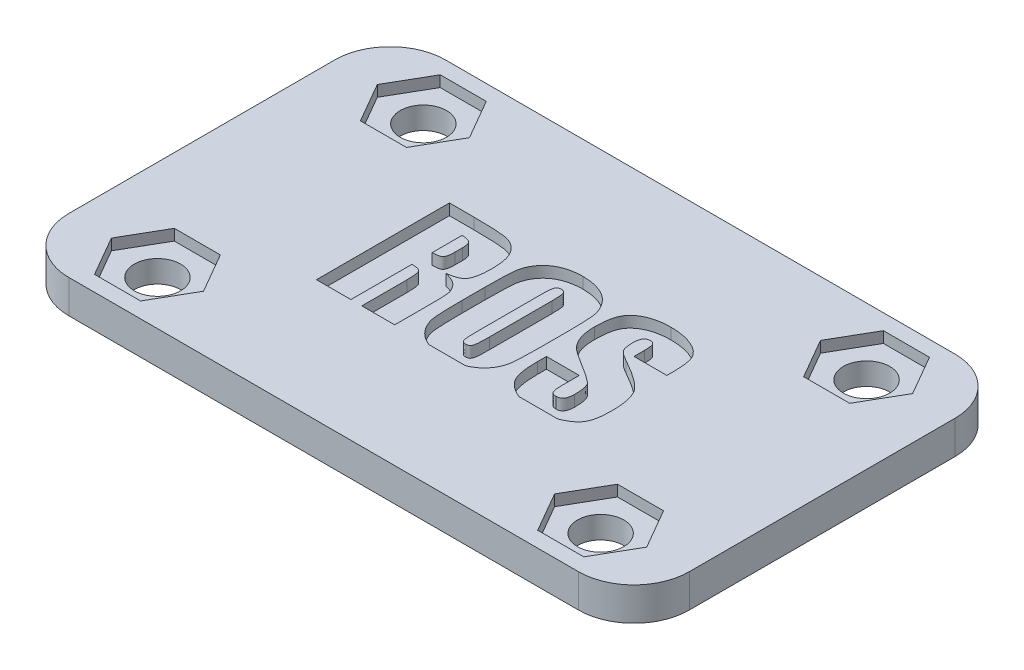
SolidWorks part; units mm, degrees
ref_plane "Front Plane" through (0, 0, 0) normal (0, 0, 1) x (1, 0, 0)
ref_plane "Top Plane" through (0, 0, 0) normal (0, 1, 0) x (1, 0, 0)
ref_plane "Right Plane" through (0, 0, 0) normal (1, 0, 0) x (0, 0, -1)
sketch "Sketch1" plane through (0, 0, 0) normal (0, 1, 0) x (1, 0, 0)
  line L1 (-28, 17) -> (28, 17)
  line L2 (-28, 17) -> (-28, -17)
  line L3 (-28, -17) -> (28, -17)
  line L4 (28, 17) -> (28, -17)
  line L5 (-28, 17) -> (28, -17) construction
  line L6 (-28, -17) -> (28, 17) construction
  point P0 (0, 0)
  dimension "D1" = 34
  dimension "D2" = 56
extrude "Boss-Extrude1" add sketch "Sketch1" along normal blind 3
sketch "Sketch2" plane through (0, 3, 0) normal (0, 1, 0) x (1, 0, 0)
  circle A0 centre (-20, 12) radius 2.09
  circle A1 centre (-20, -12) radius 2.09
  dimension "D1" = 4.18
  dimension "D2" = 24
  dimension "D3" = 12
  dimension "D4" = 20
extrude "Cut-Extrude1" cut sketch "Sketch2" against normal through all
mirror "Mirror1" about plane through (0, 0, 0) normal (1, 0, 0) of "Cut-Extrude1"
fillet "Fillet1" radius 5 4 edges at (28, 1.5, -17) (28, 1.5, 17) (-28, 1.5, 17) (-28, 1.5, -17)
sketch "Sketch3" plane through (0, 3, 0) normal (0, 1, 0) x (1, 0, 0)
  line L1 (-15.8431, 12) -> (-17.9215, 15.6)
  line L2 (-17.9215, 15.6) -> (-22.0785, 15.6)
  line L3 (-22.0785, 15.6) -> (-24.1569, 12)
  line L4 (-24.1569, 12) -> (-22.0785, 8.4)
  line L5 (-22.0785, 8.4) -> (-17.9215, 8.4)
  line L6 (-17.9215, 8.4) -> (-15.8431, 12)
  line L7 (24.1569, 12) -> (22.0785, 15.6)
  line L8 (22.0785, 15.6) -> (17.9215, 15.6)
  line L9 (17.9215, 15.6) -> (15.8431, 12)
  line L10 (15.8431, 12) -> (17.9215, 8.4)
  line L11 (17.9215, 8.4) -> (22.0785, 8.4)
  line L12 (22.0785, 8.4) -> (24.1569, 12)
  line L13 (-23, -17) -> (23, -17) construction
  circle A0 centre (-20, 12) radius 3.6 construction
  circle A1 centre (20, 12) radius 3.6 construction
  circle A2 centre (-20, 12) radius 2.09 construction
  circle A3 centre (20, 12) radius 2.09 construction
  dimension "D1" = 7.2
extrude "Cut-Extrude2" cut sketch "Sketch3" against normal blind 1
mirror "Mirror2" about plane through (0, 0, 0) normal (0, 0, 1) of "Cut-Extrude2"
sketch "Sketch4" plane through (0, 3, 0) normal (0, 1, 0) x (1, 0, 0)
  line L0 (-17, -6) -> (17, -6)
  line L1 (-11.6471, 6) -> (-9.4103, 6)
  line L2 (-4.5882, -2.7949) -> (-4.5882, -6)
  line L3 (-4.5882, -6) -> (-7.5529, -6)
  line L4 (-7.5529, -6) -> (-7.5529, -1.9412)
  line L5 (-8.5412, -0.4941) -> (-8.5412, -6)
  line L6 (-8.5412, -6) -> (-11.6471, -6)
  line L7 (-11.6471, -6) -> (-11.6471, 6)
  line L8 (-8.5412, 4.0235) -> (-8.5412, 1.3412)
  line L9 (-7.5529, 2.4287) -> (-7.5529, 3.0926)
  line L10 (-3.4588, -1.0324) -> (-3.4588, 1.0324)
  line L11 (3.7412, 1.0324) -> (3.7412, -1.0324)
  line L12 (-0.3529, 2.9757) -> (-0.3529, -2.7397)
  line L13 (0.6353, -2.6493) -> (0.6353, 2.9757)
  line L14 (11.6471, 2.3294) -> (8.6824, 2.3294)
  line L15 (8.6824, 2.3294) -> (8.6824, 3.2779)
  line L16 (4.7294, -2.4287) -> (4.7294, -1.6235)
  line L17 (4.7294, -1.6235) -> (7.6941, -1.6235)
  line L18 (7.6941, -1.6235) -> (7.6941, -3.1787)
  line L19 (11.6471, 2.8125) -> (11.6471, 2.3294)
  spline S0 degree 3 poles (-9.4103, 6) (-9.0669, 6.0012) (-8.5749, 5.9955) (-7.9492, 5.9771) (-7.5475, 5.9606) (-7.1909, 5.9363) (-6.8797, 5.9081) (-6.6138, 5.8763) (-6.3865, 5.8368) (-6.1862, 5.7853) (-6.0014, 5.7178) (-5.8245, 5.6374) (-5.6576, 5.5369) (-5.502, 5.419) (-5.352, 5.2894) (-5.2155, 5.1388) (-5.0841, 4.9743) (-4.9654, 4.7866) (-4.865, 4.5736) (-4.7788, 4.3358) (-4.7089, 4.0722) (-4.6548, 3.7831) (-4.5993, 3.3474) (-4.5915, 3.0059) (-4.5882, 2.7706) knots 0 0 0 0 0.148881 0.213303 0.271377 0.323138 0.368276 0.406827 0.439217 0.468212 0.496346 0.524443 0.552325 0.580569 0.609028 0.638128 0.668547 0.700209 0.734143 0.770448 0.80973 0.852244 0.897872 1 1 1 1
  spline S1 degree 3 poles (-4.5882, 2.7706) (-4.5847, 2.5592) (-4.5991, 2.256) (-4.6321, 1.8709) (-4.6732, 1.6245) (-4.7199, 1.4058) (-4.7787, 1.2138) (-4.8506, 1.0509) (-4.9341, 0.9125) (-5.0352, 0.7962) (-5.1554, 0.6939) (-5.2985, 0.6065) (-5.4611, 0.5289) (-5.6443, 0.4631) (-5.9295, 0.3905) (-6.1567, 0.3569) (-6.3154, 0.3441) knots 0 0 0 0 0.18379 0.264137 0.336087 0.400976 0.458649 0.510492 0.555595 0.598692 0.64408 0.692369 0.744168 0.800637 0.861472 1 1 1 1
  spline S2 degree 3 poles (-6.3154, 0.3441) (-6.1721, 0.3049) (-5.9643, 0.2494) (-5.706, 0.1522) (-5.5411, 0.0744) (-5.3931, -0.0045) (-5.2653, -0.0902) (-5.1556, -0.181) (-5.0387, -0.3053) (-4.9212, -0.4619) (-4.8041, -0.6448) (-4.7194, -0.8218) (-4.6697, -0.9719) (-4.6478, -1.1078) (-4.6293, -1.2429) (-4.6181, -1.4146) (-4.6068, -1.622) (-4.5986, -1.8647) (-4.5883, -2.2595) (-4.5915, -2.5736) (-4.5882, -2.7949) knots 0 0 0 0 0.11023 0.159227 0.204341 0.24532 0.283418 0.318243 0.350629 0.40972 0.463107 0.511383 0.554826 0.57974 0.613275 0.655917 0.707227 0.767226 0.835926 1 1 1 1
  spline S3 degree 3 poles (-7.5529, -1.9412) (-7.5542, -1.7934) (-7.554, -1.5834) (-7.5737, -1.3189) (-7.5901, -1.1553) (-7.6124, -1.0148) (-7.6369, -0.8974) (-7.67, -0.8034) (-7.7079, -0.7287) (-7.7573, -0.6684) (-7.8245, -0.6234) (-7.9036, -0.5807) (-8.0005, -0.548) (-8.1132, -0.5251) (-8.2947, -0.5004) (-8.4396, -0.4949) (-8.5412, -0.4941) knots 0 0 0 0 0.208712 0.296135 0.374434 0.440653 0.497065 0.543362 0.580978 0.614872 0.652041 0.694298 0.741574 0.795735 0.856514 1 1 1 1
  spline S4 degree 3 poles (-8.5412, 1.3412) (-8.3851, 1.3403) (-8.1682, 1.3525) (-7.9124, 1.4151) (-7.791, 1.4674) (-7.718, 1.5343) (-7.6711, 1.6021) (-7.6355, 1.6922) (-7.6049, 1.8009) (-7.5815, 1.9295) (-7.5561, 2.1403) (-7.5563, 2.3097) (-7.5529, 2.4287) knots 0 0 0 0 0.26319 0.361521 0.442778 0.481273 0.526535 0.580255 0.643242 0.716208 0.799609 1 1 1 1
  spline S5 degree 3 poles (-7.5529, 3.0926) (-7.5545, 3.251) (-7.5655, 3.4729) (-7.66, 3.7254) (-7.7586, 3.8532) (-7.9007, 3.9314) (-8.1584, 4.0148) (-8.3828, 4.0205) (-8.5412, 4.0235) knots 0 0 0 0 0.296724 0.405999 0.497474 0.590179 0.702697 1 1 1 1
  spline S6 degree 3 poles (3.7412, -1.0324) (3.7385, -1.3125) (3.74, -1.7169) (3.7317, -2.2339) (3.7191, -2.5721) (3.71, -2.8766) (3.6939, -3.1487) (3.6767, -3.3877) (3.6517, -3.661) (3.6003, -3.9749) (3.4883, -4.3317) (3.3296, -4.6711) (3.1303, -4.9928) (2.887, -5.2876) (2.6016, -5.5477) (2.2768, -5.7719) (1.913, -5.9572) (1.5147, -6.1011) (0.926, -6.2488) (0.4589, -6.2785) (0.1412, -6.2824) knots 0 0 0 0 0.112809 0.162854 0.208179 0.249065 0.285542 0.317902 0.345566 0.396043 0.445676 0.495616 0.546553 0.597656 0.649001 0.701564 0.75612 0.812885 0.871769 1 1 1 1
  spline S7 degree 3 poles (0.1412, -6.2824) (-0.1648, -6.2831) (-0.6144, -6.2452) (-1.1897, -6.1149) (-1.5848, -5.9757) (-1.9508, -5.7992) (-2.2779, -5.5765) (-2.5736, -5.321) (-2.8223, -5.0216) (-3.0318, -4.6996) (-3.1943, -4.3589) (-3.3103, -4.0053) (-3.368, -3.6952) (-3.392, -3.4245) (-3.4096, -3.1854) (-3.4246, -2.9111) (-3.4383, -2.603) (-3.4461, -2.2596) (-3.4555, -1.7324) (-3.458, -1.3191) (-3.4588, -1.0324) knots 0 0 0 0 0.123179 0.180929 0.237119 0.291548 0.344027 0.396062 0.448383 0.50021 0.550408 0.599943 0.649656 0.677029 0.709392 0.746168 0.787661 0.833574 0.884513 1 1 1 1
  spline S8 degree 3 poles (-3.4588, 1.0324) (-3.4561, 1.3132) (-3.4578, 1.7177) (-3.4492, 2.2346) (-3.437, 2.5721) (-3.4266, 2.8773) (-3.4146, 3.1495) (-3.3962, 3.3884) (-3.3721, 3.6612) (-3.3171, 3.9747) (-3.206, 4.3317) (-3.0479, 4.6709) (-2.8464, 4.9909) (-2.6056, 5.2885) (-2.3171, 5.546) (-1.9944, 5.773) (-1.63, 5.9562) (-1.2327, 6.1053) (-0.6417, 6.2443) (-0.1769, 6.2856) (0.1412, 6.2824) knots 0 0 0 0 0.1131 0.162847 0.20817 0.249054 0.28581 0.317873 0.345536 0.396062 0.445693 0.495631 0.546315 0.597643 0.649205 0.701523 0.756077 0.812942 0.872041 1 1 1 1
  spline S9 degree 3 poles (0.1412, 6.2824) (0.4469, 6.2818) (0.8967, 6.2477) (1.4702, 6.1117) (1.8645, 5.9733) (2.2316, 5.7988) (2.5599, 5.5778) (2.8536, 5.3201) (3.1028, 5.0218) (3.3114, 4.6989) (3.4772, 4.3595) (3.5927, 4.0046) (3.6506, 3.6938) (3.6735, 3.4229) (3.6959, 3.1849) (3.7057, 2.911) (3.7213, 2.6031) (3.7275, 2.2595) (3.7434, 1.7325) (3.7366, 1.3191) (3.7412, 1.0324) knots 0 0 0 0 0.123202 0.180743 0.236944 0.291253 0.343988 0.395811 0.448142 0.499979 0.550314 0.59986 0.649873 0.677251 0.709348 0.746116 0.787617 0.833538 0.884493 1 1 1 1
  spline S10 degree 3 poles (0.6353, 2.9757) (0.6349, 3.1052) (0.6314, 3.2898) (0.6236, 3.523) (0.6121, 3.6693) (0.5991, 3.7965) (0.585, 3.9051) (0.5651, 3.9935) (0.5377, 4.0836) (0.4873, 4.1724) (0.3682, 4.2858) (0.2378, 4.3035) (0.1566, 4.3059) knots 0 0 0 0 0.245382 0.350014 0.44228 0.523563 0.592561 0.649714 0.69512 0.770679 0.840726 1 1 1 1
  spline S11 degree 3 poles (0.1566, 4.3059) (0.0809, 4.3097) (-0.0301, 4.2831) (-0.155, 4.2004) (-0.2173, 4.1263) (-0.2587, 4.0467) (-0.283, 3.962) (-0.3051, 3.8552) (-0.3211, 3.7245) (-0.3378, 3.5709) (-0.3473, 3.3184) (-0.3544, 3.1178) (-0.3529, 2.9757) knots 0 0 0 0 0.141273 0.207934 0.278501 0.320511 0.375555 0.443281 0.525523 0.622695 0.733336 1 1 1 1
  spline S12 degree 3 poles (-0.3529, -2.7397) (-0.3502, -2.9007) (-0.3519, -3.1295) (-0.3437, -3.4171) (-0.331, -3.5941) (-0.3222, -3.7459) (-0.3063, -3.8724) (-0.2896, -3.9735) (-0.2657, -4.0719) (-0.2162, -4.1673) (-0.0898, -4.2859) (0.0478, -4.3054) (0.1346, -4.3059) knots 0 0 0 0 0.263966 0.37491 0.47152 0.554902 0.624119 0.680394 0.722784 0.789642 0.853612 1 1 1 1
  spline S13 degree 3 poles (0.1346, -4.3059) (0.2255, -4.3075) (0.3671, -4.2777) (0.4949, -4.1446) (0.5422, -4.0365) (0.5704, -3.9275) (0.586, -3.8179) (0.6017, -3.6841) (0.615, -3.5252) (0.6226, -3.3412) (0.6323, -3.0464) (0.6344, -2.8132) (0.6353, -2.6493) knots 0 0 0 0 0.145036 0.209347 0.281953 0.327187 0.385478 0.455017 0.538188 0.634996 0.743262 1 1 1 1
  spline S14 degree 3 poles (8.6824, 3.2779) (8.6818, 3.4588) (8.6776, 3.7029) (8.6263, 3.9859) (8.5738, 4.1183) (8.4978, 4.207) (8.3666, 4.2877) (8.2475, 4.3082) (8.1662, 4.3059) knots 0 0 0 0 0.412843 0.553103 0.65361 0.73318 0.814494 1 1 1 1
  spline S15 degree 3 poles (8.1662, 4.3059) (8.076, 4.3052) (7.9379, 4.2803) (7.7902, 4.1738) (7.6998, 4.0667) (7.6311, 3.9284) (7.5692, 3.6856) (7.549, 3.4865) (7.5529, 3.3441) knots 0 0 0 0 0.212113 0.312859 0.418563 0.535756 0.66915 1 1 1 1
  spline S16 degree 3 poles (7.5529, 3.3441) (7.5516, 3.1611) (7.5694, 2.8413) (7.6434, 2.5283) (7.7029, 2.4044) knots 0 0 0 0 0.572651 1 1 1 1
  spline S17 degree 3 poles (7.7029, 2.4044) (7.7322, 2.3452) (7.7942, 2.2581) (7.8995, 2.147) (8.0059, 2.059) (8.1288, 1.9644) (8.3296, 1.8295) (8.496, 1.7357) (8.6118, 1.6699) knots 0 0 0 0 0.166753 0.269572 0.387216 0.516182 0.662459 1 1 1 1
  spline S18 degree 3 poles (8.6118, 1.6699) (8.9472, 1.484) (9.4257, 1.211) (10.0156, 0.8328) (10.3851, 0.5738) (10.7061, 0.3313) (11.0411, 0.0406) (11.2578, -0.1815) (11.3669, -0.3397) knots 0 0 0 0 0.335278 0.4813 0.612364 0.729739 0.832713 1 1 1 1
  spline S19 degree 3 poles (11.3669, -0.3397) (11.4674, -0.4836) (11.5941, -0.7269) (11.7151, -1.0863) (11.7938, -1.3946) (11.8552, -1.7344) (11.9148, -2.2468) (11.9294, -2.6482) (11.9294, -2.925) knots 0 0 0 0 0.195997 0.304678 0.423526 0.551406 0.690506 1 1 1 1
  spline S20 degree 3 poles (11.9294, -2.925) (11.9306, -3.1274) (11.921, -3.4206) (11.8877, -3.7962) (11.8559, -4.046) (11.8113, -4.2742) (11.7592, -4.4814) (11.6979, -4.6686) (11.6247, -4.8366) (11.5365, -4.9904) (11.4313, -5.1345) (11.31, -5.2737) (11.1701, -5.4062) (11.0125, -5.5328) (10.8359, -5.6506) (10.6422, -5.7639) (10.3591, -5.9089) (9.9729, -6.059) (9.2933, -6.2392) (8.7537, -6.28) (8.3868, -6.2824) knots 0 0 0 0 0.107307 0.155459 0.199907 0.240819 0.278648 0.313174 0.345124 0.37569 0.406967 0.439576 0.4735 0.509002 0.546638 0.58596 0.627987 0.715167 0.805112 1 1 1 1
  spline S21 degree 3 poles (8.3868, -6.2824) (8.1804, -6.2854) (7.8765, -6.2668) (7.481, -6.2177) (7.2012, -6.1639) (6.9326, -6.0967) (6.6761, -6.0115) (6.43, -5.9163) (6.1998, -5.8006) (5.9838, -5.6755) (5.7857, -5.5421) (5.6073, -5.3994) (5.4478, -5.2498) (5.3077, -5.0905) (5.1891, -4.9216) (5.0852, -4.7476) (5.0057, -4.5597) (4.9402, -4.3592) (4.8815, -4.1416) (4.8378, -3.9036) (4.7968, -3.6464) (4.767, -3.3696) (4.7367, -2.9616) (4.7296, -2.6457) (4.7294, -2.4287) knots 0 0 0 0 0.100145 0.147666 0.193464 0.238409 0.281993 0.324627 0.366464 0.406944 0.445764 0.482345 0.517706 0.551866 0.585155 0.617796 0.650099 0.683973 0.720175 0.759459 0.801374 0.84664 0.894618 1 1 1 1
  spline S22 degree 3 poles (7.6941, -3.1787) (7.6926, -3.2877) (7.7, -3.4427) (7.7093, -3.6394) (7.7266, -3.7627) (7.7414, -3.871) (7.7672, -3.9619) (7.7922, -4.038) (7.8328, -4.1177) (7.9024, -4.1962) (8.0568, -4.2904) (8.2004, -4.3038) (8.2963, -4.3059) knots 0 0 0 0 0.221449 0.31586 0.400263 0.474516 0.538003 0.591926 0.637412 0.719013 0.801608 1 1 1 1
  spline S23 degree 3 poles (8.2963, -4.3059) (8.3981, -4.3086) (8.5473, -4.2778) (8.713, -4.1688) (8.8065, -4.053) (8.8803, -3.9083) (8.9485, -3.6569) (8.9647, -3.4501) (8.9647, -3.3044) knots 0 0 0 0 0.223296 0.324627 0.430189 0.546596 0.679609 1 1 1 1
  spline S24 degree 3 poles (8.9647, -3.3044) (8.9649, -3.1381) (8.9574, -2.9001) (8.9286, -2.5983) (8.8949, -2.4078) (8.857, -2.2394) (8.7927, -2.0592) (8.7313, -1.9386) (8.6757, -1.875) knots 0 0 0 0 0.336674 0.481824 0.613234 0.728042 0.830673 1 1 1 1
  spline S25 degree 3 poles (8.6757, -1.875) (8.6126, -1.8041) (8.4954, -1.699) (8.3122, -1.5594) (8.137, -1.4289) (7.9303, -1.2881) (7.5985, -1.0708) (7.3298, -0.9089) (7.1426, -0.7941) knots 0 0 0 0 0.151175 0.250667 0.367276 0.49971 0.649705 1 1 1 1
  spline S26 degree 3 poles (7.1426, -0.7941) (6.9527, -0.6788) (6.6813, -0.5122) (6.34, -0.2922) (6.1235, -0.1475) (5.9316, -0.0168) (5.767, 0.1018) (5.6269, 0.2072) (5.4751, 0.3341) (5.311, 0.5032) (5.1361, 0.7318) (4.9799, 0.9943) (4.8394, 1.2899) (4.7229, 1.6247) (4.6172, 2.1551) (4.5843, 2.5772) (4.5882, 2.8721) knots 0 0 0 0 0.139497 0.199929 0.25485 0.30299 0.345648 0.382207 0.412998 0.469794 0.529711 0.593278 0.661207 0.734924 0.815133 1 1 1 1
  spline S27 degree 3 poles (4.5882, 2.8721) (4.5915, 3.089) (4.5956, 3.4033) (4.6361, 3.8052) (4.6748, 4.0719) (4.7257, 4.3157) (4.7856, 4.5371) (4.8612, 4.7336) (4.9459, 4.9098) (5.0448, 5.0692) (5.1582, 5.2159) (5.2818, 5.3578) (5.4237, 5.4859) (5.5773, 5.6088) (5.7441, 5.7233) (5.9262, 5.8266) (6.1895, 5.9555) (6.5504, 6.088) (7.1983, 6.2468) (7.715, 6.2821) (8.0691, 6.2824) knots 0 0 0 0 0.115094 0.16642 0.214115 0.25793 0.298418 0.335563 0.369391 0.401957 0.434786 0.46765 0.501588 0.535991 0.571894 0.608743 0.64693 0.727243 0.81197 1 1 1 1
  spline S28 degree 3 poles (8.0691, 6.2824) (8.2698, 6.2794) (8.5663, 6.2747) (8.9506, 6.2262) (9.223, 6.1872) (9.4831, 6.128) (9.7326, 6.0611) (9.9699, 5.979) (10.194, 5.8841) (10.4035, 5.7811) (10.5978, 5.6745) (10.7692, 5.555) (10.9282, 5.4368) (11.0618, 5.3035) (11.1838, 5.1702) (11.2823, 5.0262) (11.3651, 4.8734) (11.4309, 4.703) (11.491, 4.5119) (11.5377, 4.2929) (11.5805, 4.0489) (11.6097, 3.7769) (11.6403, 3.3624) (11.6468, 3.0376) (11.6471, 2.8125) knots 0 0 0 0 0.103081 0.151694 0.198641 0.244219 0.288419 0.331125 0.37288 0.413199 0.450863 0.486435 0.520313 0.552325 0.583055 0.612876 0.641566 0.672036 0.706398 0.744284 0.786764 0.83346 0.884523 1 1 1 1
  point P2 (0, -6)
  dimension "D1" = 34
  dimension "D2" = 6
extrude "Cut-Extrude3" cut sketch "Sketch4" against normal blind 1 contours S3 L4 L0 L2 S2 S1 S0 L1 L7 L5 S5 L9 S4 L8 | S9 S8 L10 S7 L0 S6 L11 S13 S12 L12 S11 S10 L13 | S28 S27 S26 S25 S24 S23 S22 L18 L17 L16 S21 L0 S20 S19 S18 S17 S16 S15 S14 L15 L14 L19 region at (-8.2424, 3, -0.0304) region at (8.2206, 3, -0.0264) region at (-3.1849, 3, 3.882)
